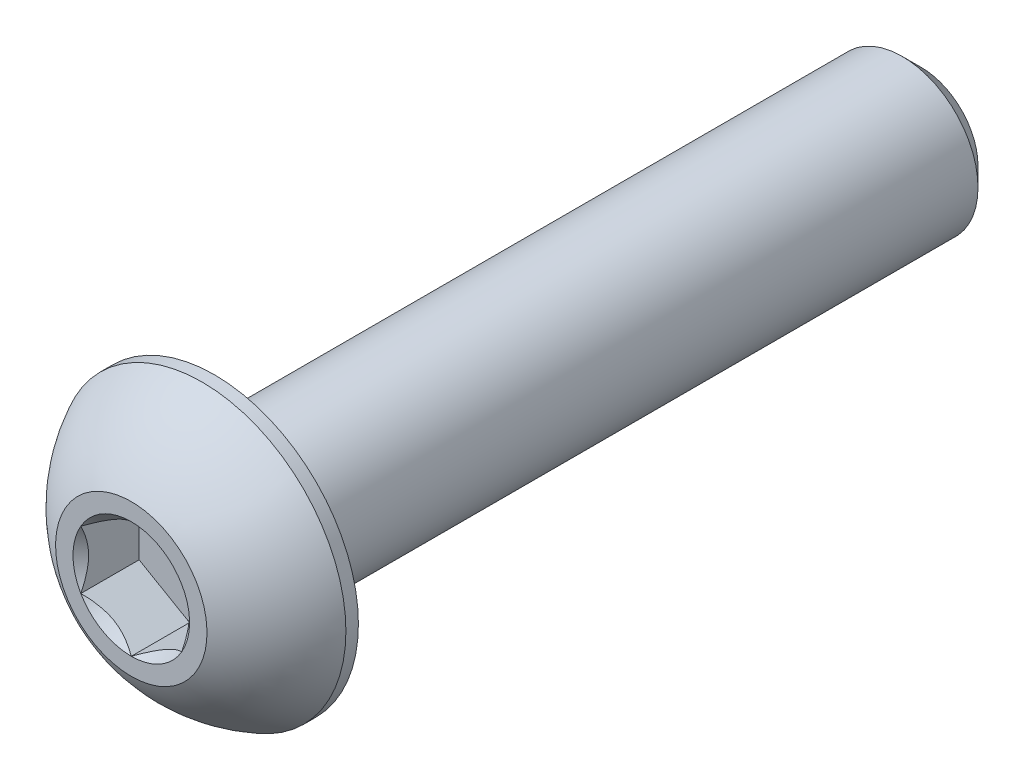
SolidWorks part; units mm, degrees
ref_plane "Front" through (0, 0, 0) normal (0, 0, 1) x (1, 0, 0)
ref_plane "Top" through (0, 0, 0) normal (0, 1, 0) x (1, 0, 0)
ref_plane "Right" through (0, 0, 0) normal (1, 0, 0) x (0, 0, -1)
sketch "Sketch1" plane through (0, 0, 0) normal (1, 0, 0) x (0, 0, -1)
  line L2 (1.65, 1.5) -> (15.65, 1.5)
  line L3 (15.65, 1.5) -> (15.65, 0)
  line L4 (15.65, 0) -> (1.65, 0)
  line L6 (1.4025, 2.85) -> (1.65, 2.85) construction
  line L7 (15.65, 1.5) -> (15.65, -1.5) construction
  line L8 (0, 0) -> (1.65, 0) construction
  line L9 (1.65, 2.85) -> (1.65, -2.85) construction
  line L11 (1.65, 1.5) -> (1.65, 0)
  line L13 (0, 1) -> (0, -1) construction
  line L14 (0, 1) -> (0, 1.5) construction
  line L15 (15.6188, 1.5541) -> (15.8688, 1.1211) construction
  line L16 (15.8688, 1.1211) -> (16.1188, 1.5541) construction
  line L17 (16.1188, 1.5541) -> (15.6188, 1.5541) construction
  line L18 (15.65, 1.5) -> (16.0875, 1.5) construction
  line L19 (15.8688, 1.5541) -> (15.8688, 1.5) construction
  line L20 (15.8688, 1.5) -> (15.8688, 1.1752) construction
  line L21 (15.8688, 1.1752) -> (15.8688, 1.1211) construction
  line L22 (15.8375, 1.1752) -> (15.9, 1.1752)
  line L23 (15.6344, 1.5271) -> (16.1031, 1.5271)
  line L24 (15.9, 1.1752) -> (16.1031, 1.5271)
  line L25 (15.8375, 1.1752) -> (15.6344, 1.5271)
  line L26 (15.275, 1.5) -> (15.65, 1.125)
  arc A3 (0, 1.5) -> (1.4025, 2.85) centre (2.7948, 0) cw construction
  point P29 (15.8688, 1.5271)
  point P30 (14.4, -1.5)
  dimension "D1" = 0.2475
  dimension "Pitch" = 0.5
  dimension "D3" = 0.0625
  dimension "D2" = 0.375
  dimension "D4" = 45
  dimension "D5" = 1.25
sketch "Sketch10" plane through (0, 0, 0) normal (1, 0, 0) x (0, 0, -1)
  line L0 (15.275, 1.5) -> (15.65, 1.125) construction
  line L1 (15.275, 1.5) -> (15.65, 1.125)
  line L4 (15.65, 1.5) -> (1.65, 1.5)
  line L5 (15.65, 0) -> (15.65, 1.5)
  line L6 (1.65, 0) -> (15.65, 0)
  line L7 (1.65, 1.5) -> (1.65, 0)
  line L8 (15.275, 1.5) -> (1.65, 1.5)
  line L9 (15.65, 0) -> (15.65, 1.125)
  line L10 (1.65, 0) -> (15.65, 0)
  line L11 (1.65, 1.5) -> (1.65, 0)
  dimension "D1" = 0
revolve "Revolve3" add sketch "Sketch10" angle 360 about L8
sketch "Sketch7" plane through (0, 0, 0) normal (1, 0, 0) x (0, 0, -1)
  line L6 (1.4025, 2.85) -> (1.65, 2.85) construction
  line L8 (0, 0) -> (1.65, 0) construction
  line L11 (1.65, 2.85) -> (1.65, -2.85) construction
  line L12 (1.4025, 2.85) -> (1.65, 2.85)
  line L13 (0, 0) -> (1.65, 0)
  line L14 (0, 1) -> (0, -1) construction
  line L15 (1.65, 2.85) -> (1.65, 0)
  line L16 (0, 1.5) -> (0, 0)
  arc A2 (1.4025, 2.85) -> (0, 1.5) centre (2.7948, 0) ccw construction
  arc A3 (1.4025, 2.85) -> (0, 1.5) centre (2.7948, 0) ccw
revolve "Revolve2" add sketch "Sketch7" angle 360 mid plane about L13
sketch "Sketch5" plane through (0, 0, 0) normal (0, 0, 1) x (1, 0, 0)
  line L1 (1, -0.5774) -> (1, 0.5774)
  line L2 (1, 0.5774) -> (0, 1.1547)
  line L3 (0, 1.1547) -> (-1, 0.5774)
  line L4 (-1, 0.5774) -> (-1, -0.5774)
  line L5 (-1, -0.5774) -> (0, -1.1547)
  line L6 (0, -1.1547) -> (1, -0.5774)
  circle A0 centre (0, 0) radius 1 construction
extrude "Cut-Extrude2" cut sketch "Sketch5" against normal blind 1.155
sketch "Sketch6" plane through (0, 0, 0) normal (0, 0, 1) x (1, 0, 0)
  circle A0 centre (0, 0) radius 1.1547
extrude "Cut-Extrude3" cut sketch "Sketch6" against normal blind 1.155 draft 45
sketch "Sketch9" [suppressed] plane through (0, 0, -1.65) normal (0, 0, -1) x (-1, 0, 0)
  circle A0 centre (0, 0) radius 1.5 construction
  circle A4 centre (0, 0) radius 1.5
split "Split1" [suppressed] bodies to split 113
sketch "Sketch11" [suppressed] plane through (0, 0, -15.65) normal (0, 0, -1) x (-1, 0, 0)
  circle A0 centre (0, 0) radius 1.5 construction
  circle A1 centre (0, 0) radius 1.5
curve "Helix/Spiral1" [suppressed] pitch 0.5 height 15.65 turns 31.3
sketch "Sketch12" [suppressed] plane through (0, 0, 0) normal (1, 0, 0) x (0, 0, -1)
  line L0 (15.8375, 1.1752) -> (15.9, 1.1752) construction
  line L1 (15.9, 1.1752) -> (16.1031, 1.5271) construction
  line L2 (15.6344, 1.5271) -> (16.1031, 1.5271) construction
  line L3 (15.8375, 1.1752) -> (15.6344, 1.5271) construction
  line L4 (15.8375, 1.1752) -> (15.9, 1.1752)
  line L5 (15.9, 1.1752) -> (16.1031, 1.5271)
  line L6 (15.6344, 1.5271) -> (16.1031, 1.5271)
  line L7 (15.8375, 1.1752) -> (15.6344, 1.5271)
sweep "Cut-Sweep2" [suppressed] cut profiles "Sketch12" path "Helix/Spiral1"
extrude "Boss-Extrude1" [suppressed] add sketch "Sketch9" along normal blind 10 draft 45
equation "\"D1@Cut-Extrude2\" = \"Head Ht@Sketch1\" * .7"
equation "\"D1@Sketch1\" = \"Head Ht@Sketch1\" * .15"
equation "\"D1@Cut-Extrude3\" = \"D1@Cut-Extrude2\""
equation "\"D3@Sketch1\" = \"Pitch@Sketch1\" / 8"
equation "\"D2@Sketch1\"=\"Pitch@Sketch1\"*0.75"
equation "\"D3@Helix/Spiral1\" = \"Lg@Sketch1\" + \"Head Ht@Sketch1\""
equation "\"D4@Helix/Spiral1\"=\"pitch@sketch1\""
equation "\"D5@Sketch1\"=\"Pitch@Sketch1\"*2.5"
